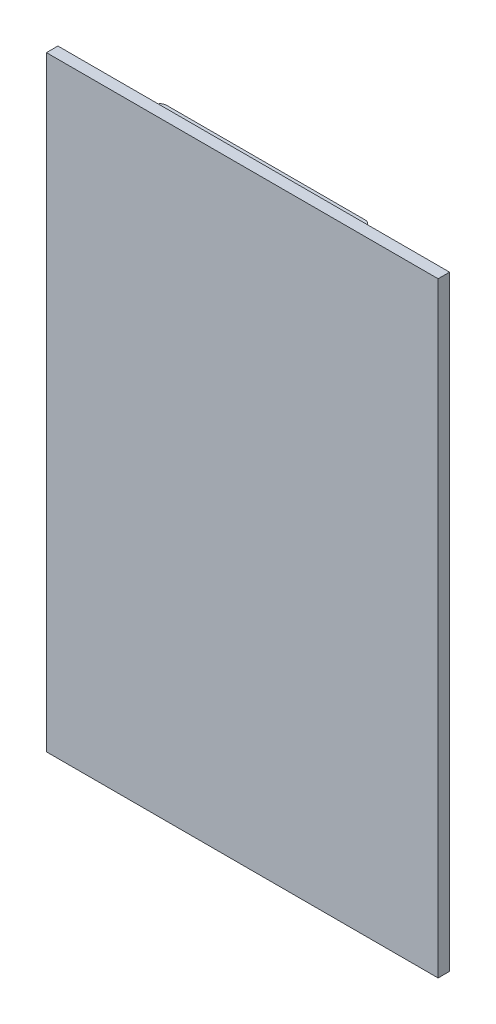
SolidWorks part; units mm, degrees
ref_plane "Front Plane" through (0, 0, 0) normal (0, 0, 1) x (1, 0, 0)
ref_plane "Top Plane" through (0, 0, 0) normal (0, 1, 0) x (1, 0, 0)
ref_plane "Right Plane" through (0, 0, 0) normal (1, 0, 0) x (0, 0, -1)
sketch "Sketch1" plane through (0, 0, 0) normal (0, 0, 1) x (1, 0, 0)
  line L1 (1.5, 102) -> (66.5, 102)
  line L2 (1.5, 102) -> (1.5, 1.5)
  line L3 (1.5, 1.5) -> (66.5, 1.5)
  line L4 (66.5, 102) -> (66.5, 1.5)
  point P4 (0, 0)
extrude "Boss-Extrude1" add sketch "Sketch1" along normal blind 1.9
sketch "Sketch2" plane through (0, 0, 0) normal (0, 0, -1) x (-1, 0, 0)
  line L0 (-66.5, 1.5) -> (-66.5, 102) construction
  line L1 (-51.5, 100.5) -> (-16.5, 100.5)
  line L2 (-51.5, 100.5) -> (-51.5, 97.5)
  line L3 (-51.5, 97.5) -> (-16.5, 97.5)
  line L4 (-16.5, 100.5) -> (-16.5, 97.5)
  line L5 (-1.5, 102) -> (-1.5, 1.5) construction
  line L6 (-66.5, 102) -> (-1.5, 102) construction
  dimension "D1" = 15
  dimension "D2" = 15
  dimension "D3" = 3
  dimension "D4" = 1.5
extrude "Boss-Extrude2" add sketch "Sketch2" along normal blind 2
fillet "Fillet2" radius 1 6 edges at (51.5, 99, 0) (34, 97.5, 0) (16.5, 99, 0) (16.5, 99, -2) (51.5, 99, -2) (34, 97.5, -2)
